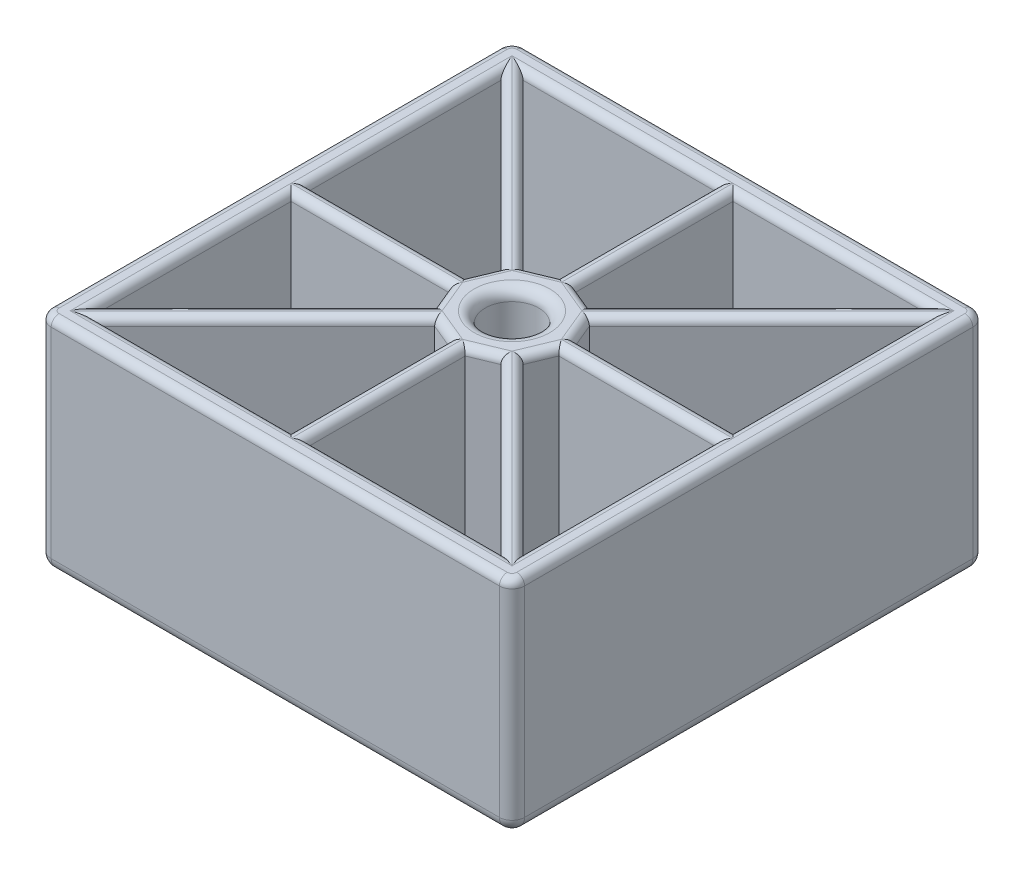
SolidWorks part; units mm, degrees
ref_plane "Front Plane" through (0, 0, 0) normal (0, 0, 1) x (1, 0, 0)
ref_plane "Top Plane" through (0, 0, 0) normal (0, 1, 0) x (1, 0, 0)
ref_plane "Right Plane" through (0, 0, 0) normal (1, 0, 0) x (0, 0, -1)
sketch "Sketch1" plane through (0, 0, 0) normal (0, 1, 0) x (1, 0, 0)
  line L1 (15, -15) -> (-15, -15)
  line L2 (15, -15) -> (15, 15)
  line L3 (15, 15) -> (-15, 15)
  line L4 (-15, -15) -> (-15, 15)
  line L5 (15, -15) -> (-15, 15) construction
  line L6 (15, 15) -> (-15, -15) construction
  point P0 (0, 0)
  dimension "D1" = 30
extrude "Boss-Extrude1" add sketch "Sketch1" along normal blind 14 contours L2 L1 L4 L3
sketch "Sketch2" plane through (0, 14, 0) normal (0, 1, 0) x (1, 0, 0)
  circle A0 centre (0, 0) radius 1.7
extrude "Cut-Extrude1" cut sketch "Sketch2" against normal blind 12
sketch "Sketch3" plane through (0, 14, 0) normal (0, 1, 0) x (1, 0, 0)
  line L0 (-15, 15) -> (15, -15) construction
  line L1 (15, 15) -> (-15, -15) construction
  line L2 (-13.5, -0.5) -> (13.5, -0.5) construction
  line L3 (13.5, -13.5) -> (-13.5, -13.5) construction
  line L4 (13.5, -13.5) -> (13.5, 13.5) construction
  line L5 (13.5, 13.5) -> (-13.5, 13.5) construction
  line L6 (-13.5, -13.5) -> (-13.5, 13.5) construction
  line L7 (13.5, -13.5) -> (-13.5, 13.5) construction
  line L8 (13.5, 13.5) -> (-13.5, -13.5) construction
  line L9 (-13.5, -0.5) -> (-13.5, 0.5) construction
  line L10 (0.5, -13.5) -> (-0.5, -13.5) construction
  line L11 (0.5, -13.5) -> (0.5, 13.5) construction
  line L12 (0.5, 13.5) -> (-0.5, 13.5) construction
  line L13 (-0.5, -13.5) -> (-0.5, 13.5) construction
  line L14 (0.5, -13.5) -> (-0.5, 13.5) construction
  line L15 (0.5, 13.5) -> (-0.5, -13.5) construction
  line L16 (-13.5, 0.5) -> (13.5, 0.5) construction
  line L17 (13.5, -0.5) -> (13.5, 0.5) construction
  line L18 (-0.5, 13.5) -> (-0.5, -13.5) construction
  line L19 (-0.5, 13.5) -> (0.5, 13.5) construction
  line L20 (0.5, 13.5) -> (0.5, -13.5) construction
  line L21 (-0.5, -13.5) -> (0.5, -13.5) construction
  line L22 (13.5, 0.5) -> (-13.5, 0.5) construction
  line L23 (13.5, 0.5) -> (13.5, -0.5) construction
  line L24 (13.5, -0.5) -> (-13.5, -0.5) construction
  line L25 (-13.5, 0.5) -> (-13.5, -0.5) construction
  line L26 (9.8995, -9.1924) -> (-9.1924, 9.8995) construction
  line L27 (-9.1924, 9.8995) -> (-9.8995, 9.1924) construction
  line L28 (9.1924, -9.8995) -> (-9.8995, 9.1924) construction
  line L29 (9.8995, -9.1924) -> (9.1924, -9.8995) construction
  line L30 (-9.1924, -9.8995) -> (9.8995, 9.1924) construction
  line L31 (-9.1924, -9.8995) -> (-9.8995, -9.1924) construction
  line L32 (-9.8995, -9.1924) -> (9.1924, 9.8995) construction
  line L33 (9.8995, 9.1924) -> (9.1924, 9.8995) construction
  line L34 (2.0959, 2.803) -> (12.7929, 13.5)
  line L35 (12.7929, 13.5) -> (0.5, 13.5)
  line L36 (0.5, 13.5) -> (0.5, 3.4641)
  line L37 (2.803, 2.0959) -> (13.5, 12.7929)
  line L38 (13.5, 12.7929) -> (13.5, 0.5)
  line L39 (13.5, 0.5) -> (3.4641, 0.5)
  line L40 (3.4641, -0.5) -> (13.5, -0.5)
  line L41 (2.803, -2.0959) -> (13.5, -12.7929)
  line L42 (13.5, -12.7929) -> (13.5, -0.5)
  line L43 (2.0959, -2.803) -> (12.7929, -13.5)
  line L44 (12.7929, -13.5) -> (0.5, -13.5)
  line L45 (0.5, -13.5) -> (0.5, -3.4641)
  line L46 (-2.0959, -2.803) -> (-12.7929, -13.5)
  line L47 (-12.7929, -13.5) -> (-0.5, -13.5)
  line L48 (-0.5, -13.5) -> (-0.5, -3.4641)
  line L49 (-2.803, -2.0959) -> (-13.5, -12.7929)
  line L50 (-13.5, -12.7929) -> (-13.5, -0.5)
  line L51 (-13.5, -0.5) -> (-3.4641, -0.5)
  line L52 (-2.803, 2.0959) -> (-13.5, 12.7929)
  line L53 (-13.5, 12.7929) -> (-13.5, 0.5)
  line L54 (-13.5, 0.5) -> (-3.4641, 0.5)
  line L55 (-2.0959, 2.803) -> (-12.7929, 13.5)
  line L56 (-12.7929, 13.5) -> (-0.5, 13.5)
  line L57 (-0.5, 13.5) -> (-0.5, 3.4641)
  line L58 (2.0959, 2.803) -> (0.5, 3.4641)
  line L59 (-0.5, 3.4641) -> (-2.0959, 2.803)
  line L60 (-2.803, 2.0959) -> (-3.4641, 0.5)
  line L61 (-2.803, -2.0959) -> (-3.4641, -0.5)
  line L62 (-2.0959, -2.803) -> (-0.5, -3.4641)
  line L63 (0.5, -3.4641) -> (2.0959, -2.803)
  line L64 (2.803, -2.0959) -> (3.4641, -0.5)
  line L65 (3.4641, 0.5) -> (2.803, 2.0959)
  point P8 (0, 0)
  point P16 (0, 0)
  point P34 (0, 0)
  point P42 (0, 0)
  dimension "D1" = 1
  dimension "D2" = 4
  dimension "D3" = 2
extrude "Cut-Extrude2" cut sketch "Sketch3" against normal blind 11
fillet "Fillet1" radius 0.7 1 edges at (0, 14, 1.7)
fillet "Fillet2" radius 0.5 36 edges at (15, 14, 0) (0, 14, 15) (-15, 14, 0) (0, 14, -15) (-7.4444, 14, -8.1515) (-1.298, 14, -3.1336) (-0.5, 14, -8.4821) (-6.6464, 14, -13.5) (3.1336, 14, 1.298) (8.1515, 14, 7.4444) (13.5, 14, 6.6464) (8.4821, 14, 0.5) (-8.1515, 14, -7.4444) (-13.5, 14, -6.6464) (-8.4821, 14, -0.5) (-3.1336, 14, -1.298) (-8.1515, 14, 7.4444) (-3.1336, 14, 1.298) (-8.4821, 14, 0.5) (-13.5, 14, 6.6464) (7.4444, 14, 8.1515) (1.298, 14, 3.1336) (0.5, 14, 8.4821) (6.6464, 14, 13.5) (7.4444, 14, -8.1515) (6.6464, 14, -13.5) (0.5, 14, -8.4821) (1.298, 14, -3.1336) (-7.4444, 14, 8.1515) (-6.6464, 14, 13.5) (-0.5, 14, 8.4821) (-1.298, 14, 3.1336) (8.1515, 14, -7.4444) (3.1336, 14, -1.298) (8.4821, 14, -0.5) (13.5, 14, -6.6464)
fillet "Fillet3" radius 0.8 4 edges at (-15, 0, 0) (0, 0, 15) (15, 0, 0) (0, 0, -15)
fillet "Fillet4" radius 0.8 12 edges at (-14.8536, 13.8536, -14.8536) (-14.8536, 13.8536, 14.8536) (14.8536, 13.8536, -14.8536) (14.8536, 13.8536, 14.8536) (14.7657, 0.2343, 14.7657) (14.7657, 0.2343, -14.7657) (-14.7657, 0.2343, 14.7657) (-14.7657, 0.2343, -14.7657) (15, 7.15, 15) (15, 7.15, -15) (-15, 7.15, 15) (-15, 7.15, -15)
sketch "Sketch4" plane through (0, 0, 0) normal (0, -1, 0) x (1, 0, 0)
  line L0 (0, 14.2) -> (0, -14.2) construction
  line L1 (14.2, 14.2) -> (-14.2, 14.2) construction
  line L2 (-14.2, -14.2) -> (14.2, -14.2) construction
  line L3 (-14.2, 0) -> (14.2, 0) construction
  line L4 (-14.2, 14.2) -> (-14.2, -14.2) construction
  line L5 (14.2, -14.2) -> (14.2, 14.2) construction
  line L7 (-33.2134, 4.0245) -> (33.2134, 4.0245) construction
  line L8 (-33.2134, 4.0245) -> (-33.2134, -4.0245) construction
  line L9 (-33.2134, -4.0245) -> (33.2134, -4.0245) construction
  line L10 (33.2134, 4.0245) -> (33.2134, -4.0245) construction
  line L11 (-33.2134, 4.0245) -> (33.2134, -4.0245) construction
  line L12 (-33.2134, -4.0245) -> (33.2134, 4.0245) construction
  text T0 "חימום" font "Courier New" height in points 28
  point P12 (0, 0)
  point P17 (0, 0)
  point P19 (0, 0)
  point P20 (0, 0)
  point P21 (0, 0)
  point P23 (0, 0)
  point P24 (0, 0)
  point P25 (0, 0)
  point P26 (0, 0)
  point P27 (0, 0)
  point P28 (0, 0)
  dimension "D1" = 8.049
